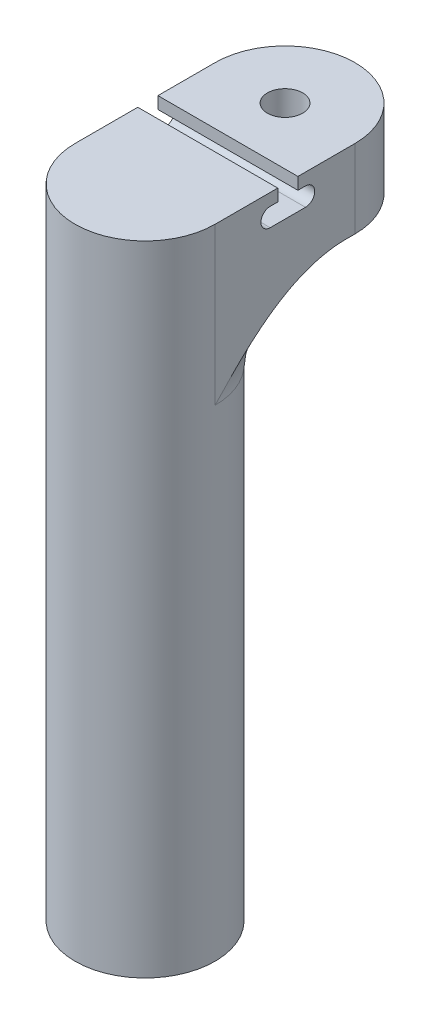
SolidWorks part; units mm, degrees
ref_plane "Front Plane" through (0, 0, 0) normal (0, 0, 1) x (1, 0, 0)
ref_plane "Top Plane" through (0, 0, 0) normal (0, 1, 0) x (1, 0, 0)
ref_plane "Right Plane" through (0, 0, 0) normal (1, 0, 0) x (0, 0, -1)
sketch "Sketch1" plane through (0, 0, 0) normal (0, 1, 0) x (1, 0, 0)
  circle A0 centre (0, 0) radius 12.5
  dimension "D1" = 25
extrude "Boss-Extrude1" add sketch "Sketch1" along normal blind 100
sketch "Sketch3" plane through (0, 0, 0) normal (0, -1, 0) x (1, 0, 0)
  line L1 (4.1, -4.1) -> (-4.1, -4.1)
  line L2 (4.1, -4.1) -> (4.1, 4.1)
  line L3 (4.1, 4.1) -> (-4.1, 4.1)
  line L4 (-4.1, -4.1) -> (-4.1, 4.1)
  line L5 (4.1, -4.1) -> (-4.1, 4.1) construction
  line L6 (4.1, 4.1) -> (-4.1, -4.1) construction
  point P0 (0, 0)
  dimension "D1" = 8.2
  dimension "D2" = 8.2
extrude "Cut-Extrude1" cut sketch "Sketch3" against normal blind 20
sketch "Sketch4" plane through (0, 100, 0) normal (0, 1, 0) x (1, 0, 0)
  line L0 (0, 0) -> (0, 25) construction
  line L5 (-12.5, 0) -> (-12.5, 25)
  line L6 (12.5, 0) -> (12.5, 25)
  arc A0 (-12.5, 0) -> (12.5, 0) centre (0, 0) ccw
  arc A1 (12.5, 25) -> (-12.5, 25) centre (0, 25) ccw
  point P2 (0, 12.5)
  dimension "D1" = 12.5
  dimension "D2" = 25
extrude "Boss-Extrude2" add sketch "Sketch4" along normal blind 14
sketch "Sketch5" plane through (0, 100, 0) normal (0, -1, 0) x (1, 0, 0)
  line L0 (-12.5, -25) -> (-12.5, 0) construction
  arc A0 (-12.5, -25) -> (12.5, -25) centre (0, -25) ccw construction
  circle A1 centre (0, -25) radius 5.15
  point P0 (0, -25)
  dimension "D3" = 10.3
  dimension "D1" = 0
  dimension "D2" = 12.5
extrude "Cut-Extrude2" cut sketch "Sketch5" against normal blind 8.8
sketch "Sketch6" plane through (0, 108.8, 0) normal (0, -1, 0) x (1, 0, 0)
  circle A0 centre (0, -25) radius 3.15
  point P0 (0, -25)
  dimension "D1" = 6.3
extrude "Cut-Extrude4" cut sketch "Sketch6" against normal up to surface (5.2 mm away) up to face at (0, 114, -12.5)
sketch "Sketch7" plane through (12.5, 0, 0) normal (1, 0, 0) x (0, 0, -1)
  line L0 (9.85, 110.2) -> (16.15, 110.2) construction
  line L1 (9.85, 111.85) -> (11.2, 111.85)
  line L2 (9.85, 108.55) -> (16.15, 108.55)
  line L3 (25, 114) -> (25, 100) construction
  line L4 (0, 114) -> (25, 114) construction
  line L5 (13, 110.2) -> (13, 114) construction
  line L6 (13, 114) -> (11.2, 114)
  line L7 (11.2, 114) -> (11.2, 111.85)
  line L8 (13, 114) -> (14.8, 114)
  line L9 (14.8, 114) -> (14.8, 111.85)
  line L10 (14.8, 111.85) -> (16.15, 111.85)
  arc A0 (9.85, 111.85) -> (9.85, 108.55) centre (9.85, 110.2) ccw
  arc A1 (16.15, 108.55) -> (16.15, 111.85) centre (16.15, 110.2) ccw
  point P2 (13, 110.2)
  dimension "D1" = 3.3
  dimension "D2" = 6.3
  dimension "D3" = 12
  dimension "D4" = 3.8
  dimension "D5" = 1.8
  dimension "D6" = 1.8
  dimension "D7" = 0
extrude "Cut-Extrude5" cut sketch "Sketch7" against normal up to surface (25 mm away) up to face at (-12.5, 107, -12.5)
fillet "Fillet1" radius 14 1 edges at (0, 100, -12.5) type face fillet first side face at (0, 100, -30.15) second side face at (0, 107, 0)
